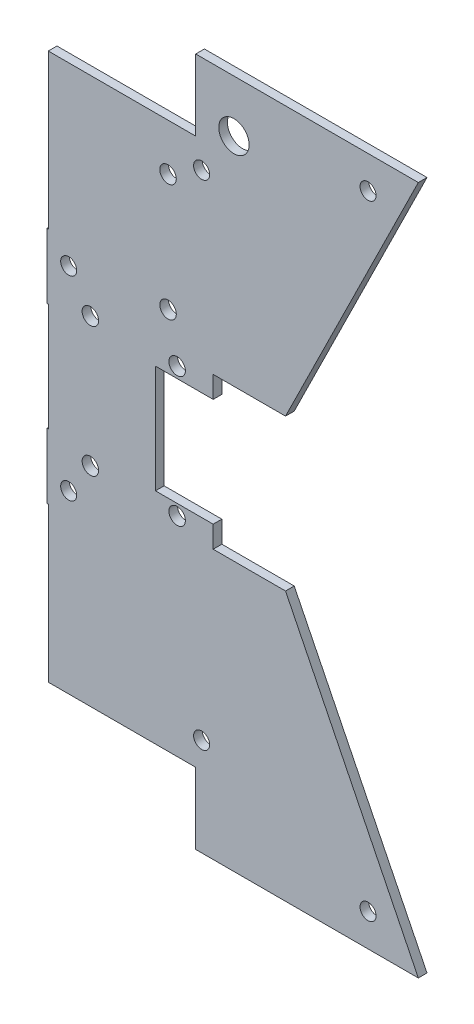
SolidWorks part; units mm, degrees
material "Thornel Mat VMA"
ref_plane "Front Plane" through (0, 0, 0) normal (0, 0, 1) x (1, 0, 0)
ref_plane "Top Plane" through (0, 0, 0) normal (0, 1, 0) x (1, 0, 0)
ref_plane "Right Plane" through (0, 0, 0) normal (1, 0, 0) x (0, 0, -1)
sketch "Sketch1" plane through (0, 0, 0) normal (0, 0, 1) x (1, 0, 0)
  line L0 (-2.9301, -104.5098) -> (-3.3149, -104.5098)
  line L1 (-3.3149, -72.8868) -> (-2.9301, -72.8868)
  line L78 (45.3299, -66.5368) -> (45.3299, -72.8868)
  line L79 (45.3299, -104.5098) -> (45.3299, -110.8598)
  line L80 (66.5174, -66.5368) -> (105.3971, 12.1397)
  line L81 (105.3971, 12.1397) -> (38.7094, 12.1397)
  line L88 (38.7094, 12.1397) -> (38.7094, -8.6883)
  line L89 (-2.9301, -8.6883) -> (38.7094, -8.6883)
  line L90 (-3.3149, -53.8368) -> (-2.9301, -53.8368)
  line L91 (-2.9301, -53.8368) -> (-2.9301, -8.6883)
  line L92 (-3.3149, -66.5368) -> (-3.3149, -53.8368)
  line L93 (-3.3149, -72.8868) -> (-3.3149, -66.5368)
  line L94 (-2.9301, -104.5098) -> (-2.9301, -72.8868)
  line L95 (-3.3149, -110.8598) -> (-3.3149, -104.5098)
  line L96 (66.5174, -110.8598) -> (105.3971, -189.5363)
  line L97 (105.3971, -189.5363) -> (38.7094, -189.5363)
  line L98 (38.7094, -189.5363) -> (38.7094, -168.7083)
  line L99 (-2.9301, -168.7083) -> (38.7094, -168.7083)
  line L106 (-3.3149, -110.8598) -> (-3.3149, -123.5598)
  line L107 (-3.3149, -123.5598) -> (-2.9301, -123.5598)
  line L108 (66.5174, -110.8598) -> (45.3299, -110.8598)
  line L109 (45.3299, -66.5368) -> (66.5174, -66.5368)
  line L110 (45.3299, -104.5098) -> (45.3299, -72.8868)
  line L111 (-2.9301, -123.5598) -> (-2.9301, -168.7083)
  circle A0 centre (90.6739, 2.6147) radius 2.3495
  circle A1 centre (41.9566, -16.4353) radius 2.3495
  circle A2 centre (3.0351, -60.1868) radius 2.3495
  circle A3 centre (3.0351, -117.2098) radius 2.3495
  circle A4 centre (41.9566, -160.9613) radius 2.3495
  circle A5 centre (90.6739, -180.0113) radius 2.3495
  circle A6 centre (51.4094, -3.1003) radius 4.445
  point P2 (90.6739, 2.6147)
  point P4 (41.9566, -16.4353)
  point P6 (3.0351, -60.1868)
  point P8 (3.0351, -117.2098)
  point P10 (41.9566, -160.9613)
  point P11 (90.6739, -180.0113)
  point P20 (0, 0)
  dimension "D2" = 4.699
  dimension "D5" = 8.89
  dimension "D1" = 66.6876
  dimension "D3" = 12.7
  dimension "D4" = 15.24
  dimension "D6" = 48.26
extrude "Boss-Extrude1" add sketch "Sketch1" along normal blind 2.54
sketch "Sketch2" plane through (0, 0, 2.54) normal (0, 0, 1) x (1, 0, 0)
  line L0 (-3.3149, -53.8368) -> (-3.3149, -72.8868) construction
  line L1 (45.3299, -66.5368) -> (66.5174, -66.5368) construction
  line L2 (45.3299, -88.6983) -> (-2.9301, -88.6983) construction
  line L3 (45.3299, -110.8598) -> (45.3299, -66.5368) construction
  line L4 (-2.9301, -72.8868) -> (-2.9301, -104.5098) construction
  circle A0 centre (9.3851, -69.7118) radius 2.413
  circle A2 centre (34.7851, -69.7118) radius 2.413
  circle A4 centre (34.7851, -107.6848) radius 2.413
  circle A6 centre (9.3851, -107.6848) radius 2.413
  dimension "D1" = 4.826
  dimension "D2" = 25.4
  dimension "D3" = 4.826
  dimension "D5" = 12.7
  dimension "D7" = 3.175
extrude "Cut-Extrude1" cut sketch "Sketch2" against normal through all
sketch "Sketch3" plane through (0, 0, 2.54) normal (0, 0, 1) x (1, 0, 0)
  line L0 (45.3299, -110.8598) -> (45.3299, -66.5368) construction
  line L1 (45.3299, -72.8868) -> (28.4351, -72.8868)
  line L2 (45.3299, -72.8868) -> (45.3299, -104.5098)
  line L3 (45.3299, -104.5098) -> (28.4351, -104.5098)
  line L4 (28.4351, -72.8868) -> (28.4351, -104.5098)
  line L5 (45.3299, -66.5368) -> (66.5174, -66.5368) construction
  line L6 (66.5174, -110.8598) -> (45.3299, -110.8598) construction
  circle A1 centre (9.3851, -69.7118) radius 2.413 construction
  dimension "D3" = 19.05
  dimension "D1" = 6.35
  dimension "D2" = 6.35
extrude "Cut-Extrude2" cut sketch "Sketch3" against normal through all
sketch "Sketch4" plane through (0, 0, 2.54) normal (0, 0, 1) x (1, 0, 0)
  line L0 (-2.9301, -168.7083) -> (38.7094, -168.7083) construction
  line L1 (27.4577, 15.7469) -> (40.2334, 15.7469)
  line L2 (27.4577, 15.7469) -> (27.4577, -8.6883)
  line L3 (27.4577, -8.6883) -> (40.2334, -8.6883)
  line L4 (40.2334, 15.7469) -> (40.2334, -8.6883)
  line L5 (0, -197.042) -> (40.2334, -197.042)
  line L6 (0, -197.042) -> (0, -168.7083)
  line L7 (0, -168.7083) -> (40.2334, -168.7083)
  line L8 (40.2334, -197.042) -> (40.2334, -168.7083)
  line L9 (38.7094, -168.7083) -> (38.7094, -189.5363) construction
  line L10 (38.7094, -8.6883) -> (-2.9301, -8.6883) construction
  dimension "D1" = 1.524
extrude "Cut-Extrude3" cut sketch "Sketch4" against normal through all
sketch "Sketch5" plane through (0, 0, 0) normal (0, 0, -1) x (-1, 0, 0)
  line L0 (2.9301, -8.6883) -> (2.9301, -53.8368) construction
  line L1 (-40.2334, -8.6883) -> (2.9301, -8.6883) construction
  circle A0 centre (-32.1219, -22.4043) radius 2.413
  circle A1 centre (-32.1219, -56.6943) radius 2.413
  dimension "D4" = 4.826
  dimension "D1" = 35.052
  dimension "D2" = 13.716
  dimension "D3" = 34.29
extrude "Cut-Extrude4" cut sketch "Sketch5" against normal through all
